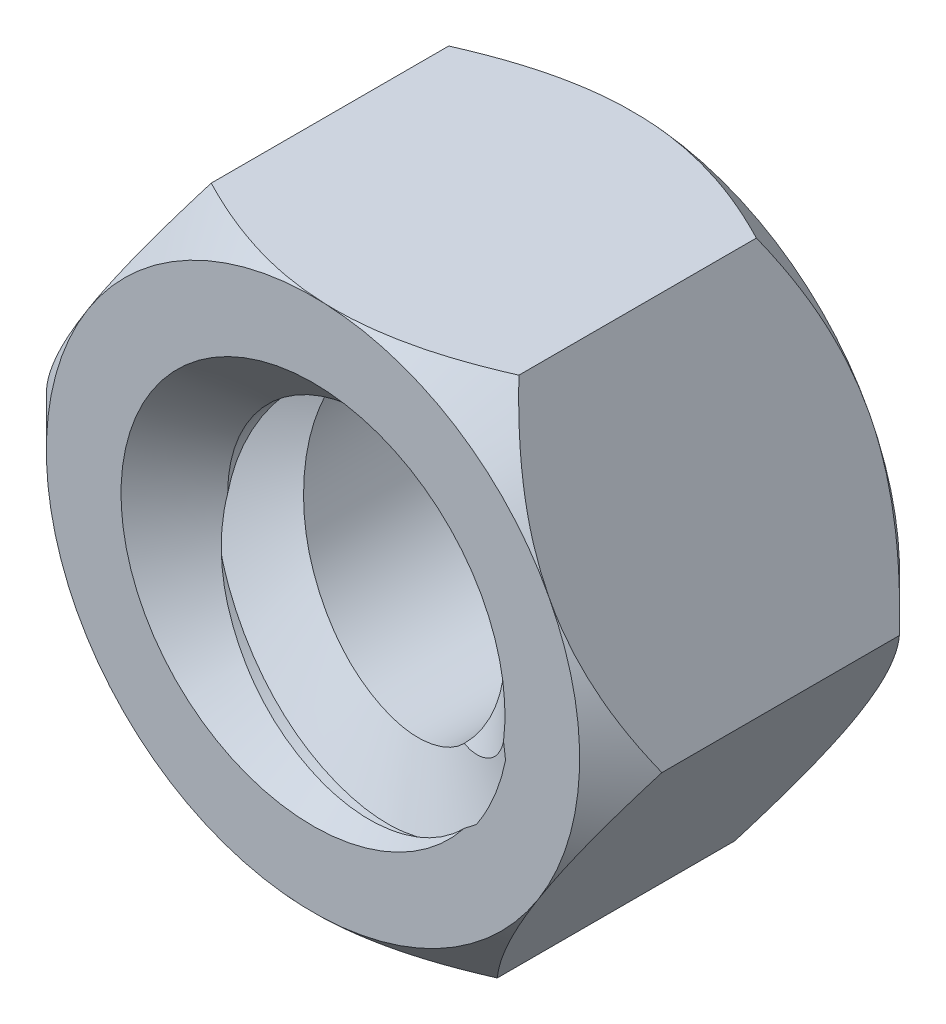
SolidWorks part; units mm, degrees
ref_plane "Front Plane" through (0, 0, 0) normal (0, 0, 1) x (1, 0, 0)
ref_plane "Top Plane" through (0, 0, 0) normal (0, 1, 0) x (1, 0, 0)
ref_plane "Right Plane" through (0, 0, 0) normal (1, 0, 0) x (0, 0, -1)
sketch "Sketch1" plane through (0, 0, 0) normal (0, 0, 1) x (1, 0, 0)
  line L1 (1.3408, -2.5565) -> (2.8844, -0.117)
  line L2 (2.8844, -0.117) -> (1.5435, 2.4394)
  line L3 (1.5435, 2.4394) -> (-1.3408, 2.5565)
  line L4 (-1.3408, 2.5565) -> (-2.8844, 0.117)
  line L5 (-2.8844, 0.117) -> (-1.5435, -2.4394)
  line L6 (-1.5435, -2.4394) -> (1.3408, -2.5565)
  circle A0 centre (0, 0) radius 2.5 construction
  dimension "D1" = 5
extrude "Boss-Extrude1" add sketch "Sketch1" along normal mid plane 3
sketch "Sketch2" plane through (0, 0, 1.5) normal (0, 0, 1) x (1, 0, 0)
  line L0 (-1.3408, 2.5565) -> (-2.8844, 0.117) construction
  circle A0 centre (0, 0) radius 2.5
extrude "Cut-Extrude1" cut sketch "Sketch2" against normal through all draft 45 flip side to cut
mirror "Mirror1" about plane through (0, 0, 0) normal (0, 0, 1) of "Cut-Extrude1"
sketch "Sketch3" plane through (0, 0, 1.5) normal (0, 0, 1) x (1, 0, 0)
  circle A0 centre (0, 0) radius 1.3
  dimension "D1" = 2.6
extrude "Cut-Extrude2" cut sketch "Sketch3" against normal through all
chamfer "Chamfer1" distance 0.5 angle 45 2 edges at (1.3, 0, -1.5) (1.3, 0, 1.5)
thread "Thread1" pitch 1 method cut profile "Thread Profile1" start angle 0, offset 2, length 0, pitch 2, diameter 2.6
ref_plane "Plane1" through (-1.3, 0, 3) normal (0, -1, 0) x (-1, 0, 0)
sketch "Thread Profile1" plane through (-1.3, 0, 3) normal (0, -1, 0) x (-1, 0, 0)
  line L0 (0, 0) -> (0, 1) construction
  line L1 (0, 0) -> (0.5413, 0.3125)
  line L2 (0.5413, 0.3125) -> (0.5413, 0.4375)
  line L3 (0.5413, 0.4375) -> (0, 0.75)
  line L4 (0.5413, 0.375) -> (0, 0.375) construction
  line L11 (0, 0) -> (0, 0.75)
  point P2 (0, 0)
  dimension "Pitch" = 1
  dimension "Profile_Angle" = 60
  dimension "Profile_Land" = 0.125
  dimension "Profile_Height" = 0.5413
scale "Scale1" bodies to scale 105 scale about centroid uniform scaling yes scale factor 0.8
